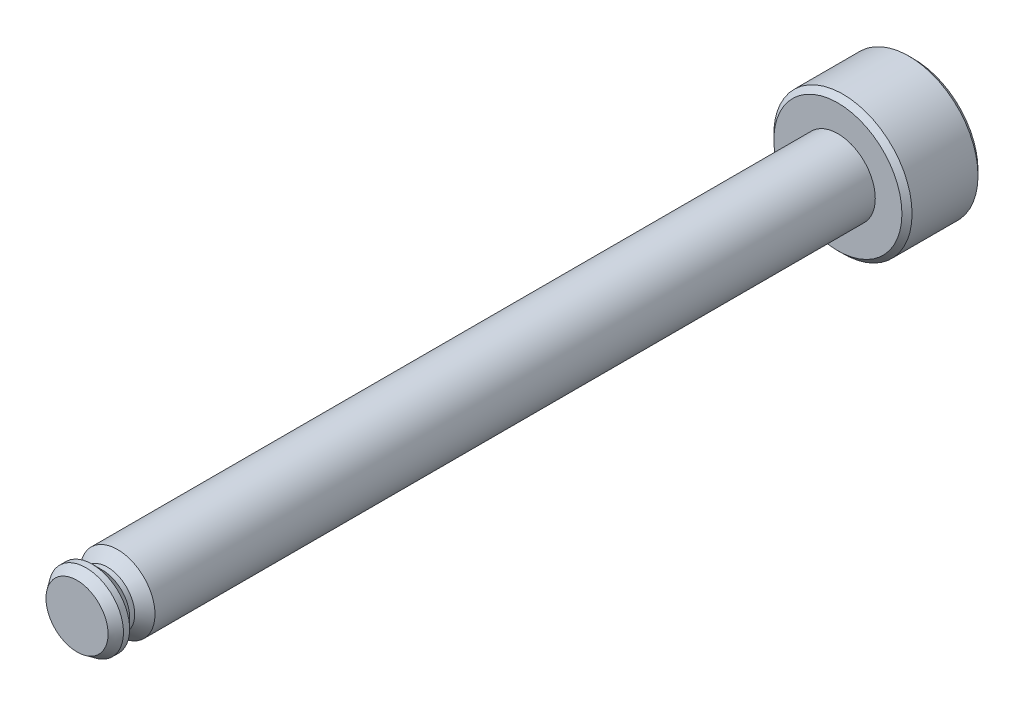
SolidWorks part; units mm, degrees
ref_plane "Front" through (0, 0, 0) normal (0, 0, 1) x (1, 0, 0)
ref_plane "Top" through (0, 0, 0) normal (0, 1, 0) x (1, 0, 0)
ref_plane "Right" through (0, 0, 0) normal (1, 0, 0) x (0, 0, -1)
sketch "Sketch2" plane through (0, 0, 0) normal (0, 0, 1) x (1, 0, 0)
  circle A0 centre (0, 0) radius 1.475
  dimension "D1" = 2.95
extrude "Shaft" add sketch "Sketch2" along normal blind 30
sketch "Sketch5" plane through (0, 0, 0) normal (0, 0, 1) x (1, 0, 0)
  circle A0 centre (0, 0) radius 2.725
  dimension "D1" = 5.45
extrude "Head" add sketch "Sketch5" against normal blind 3
sketch "Sketch4" plane through (0, 0, 0) normal (1, 0, 0) x (0, 0, -1)
  line L0 (0, 0) -> (-18.9, 0) construction
  line L1 (-18.9, 0) -> (-18.9, 4.3666) construction
  line L2 (-19.4, 1.475) -> (-18.4, 1.475)
  line L3 (0, 1.475) -> (-30, 1.475) construction
  line L6 (-18.4, 1.475) -> (-18.8, 1.075)
  line L7 (-18.8, 1.075) -> (-19, 1.075)
  line L8 (-19, 1.075) -> (-19.4, 1.475)
  line L10 (-18.9, 50) -> (-18.9, -50) construction
  dimension "D2" = 1
  dimension "D3" = 45
  dimension "D4" = 0.4
revolve "e-Clip Notch Short" [suppressed] cut sketch "Sketch4" angle 360 about L0
chamfer "Chamfer1" distance 0.25 angle 55 1 edges at (1.475, 0, 30) first distance on face at (1.475, 0, 30)
chamfer "Deburs" distance 0.2 angle 45 2 edges at (2.725, 0, 0) (2.725, 0, -3)
sketch "Sketch6" plane through (0, 0, 0) normal (1, 0, 0) x (0, 0, -1)
  line L0 (0, 0) -> (-28.9, 0) construction
  line L1 (-28.9, 0) -> (-28.9, 1.075) construction
  line L2 (0, 1.475) -> (-29.643, 1.475) construction
  line L3 (-29.4, 1.475) -> (-28.4, 1.475)
  line L4 (-28.4, 1.475) -> (-28.8, 1.075)
  line L5 (-28.8, 1.075) -> (-29, 1.075)
  line L6 (-29, 1.075) -> (-29.4, 1.475)
  line L7 (-28.9, 1.075) -> (-28.9, 1.475) construction
  line L8 (-19.4, 1.475) -> (-18.4, 1.475) construction
  line L9 (-19, 1.075) -> (-19.4, 1.475) construction
  line L10 (-28.9, 50) -> (-28.9, -50) construction
revolve "e-Clip Notch Long" cut sketch "Sketch6" angle 360 about L0
equation "\"D1@Sketch2\"=\"Plastic Hardware OD@Box Assy.Assembly\""
equation "\"D1@Sketch5\"=\"Hardware Head Countersink Diameter@Box Assy.Assembly\"-.3mm"
equation "\"D1@Head\"=\"Countersink Depth@Box Assy.Assembly\""
